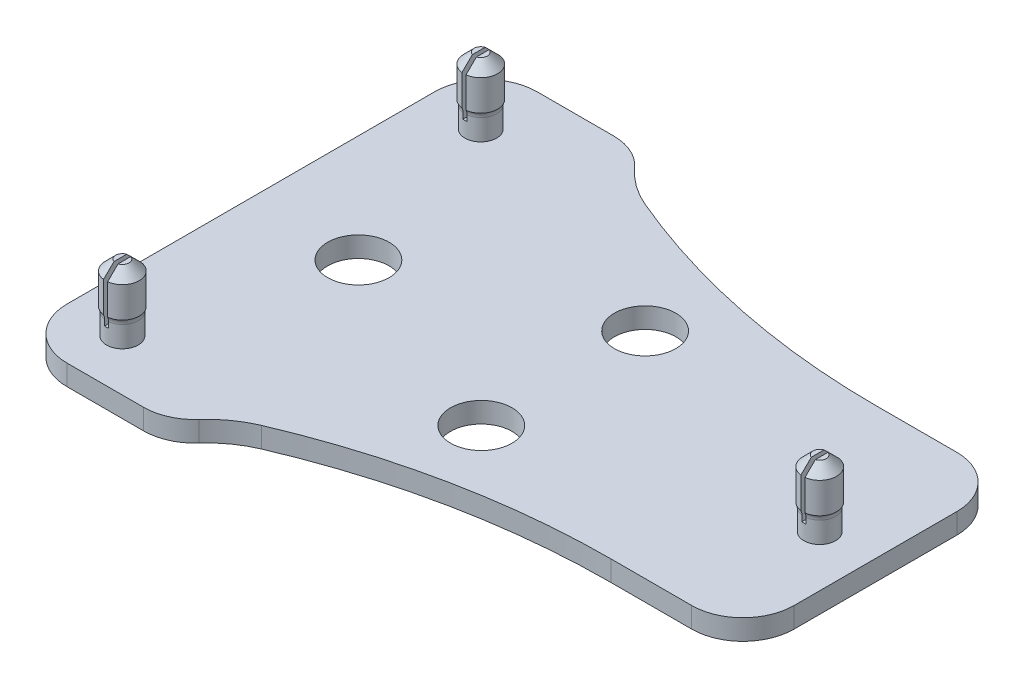
SolidWorks part; units mm, degrees
ref_plane "Front Plane" through (0, 0, 0) normal (0, 0, 1) x (1, 0, 0)
ref_plane "Top Plane" through (0, 0, 0) normal (0, 1, 0) x (1, 0, 0)
ref_plane "Right Plane" through (0, 0, 0) normal (1, 0, 0) x (0, 0, -1)
sketch "Sketch1" plane through (0, 0, 0) normal (0, 1, 0) x (1, 0, 0)
  line L0 (-30.5, -22.95) -> (-30.5, 22.95)
  line L1 (28.5, -20.95) -> (-28.5, -20.95) construction
  line L2 (28.5, -20.95) -> (28.5, 20.95) construction
  line L3 (28.5, 20.95) -> (-28.5, 20.95) construction
  line L4 (-28.5, -20.95) -> (-28.5, 20.95) construction
  line L5 (28.5, -20.95) -> (-28.5, 20.95) construction
  line L6 (28.5, 20.95) -> (-28.5, -20.95) construction
  line L7 (-15.5, 22.95) -> (-30.5, 22.95)
  line L8 (30.5, -12.95) -> (30.5, 12.95)
  line L9 (-15.5, -22.95) -> (-30.5, -22.95)
  line L10 (0, 0) -> (-42.2176, 0) construction
  line L11 (-15.5, 22.95) -> (-15.5, 11.3939) construction
  line L12 (30.5, 12.95) -> (17.6169, 12.95) construction
  line L13 (17.6169, 12.95) -> (-11.7527, 12.95) construction
  line L14 (-15.5, 22.95) -> (-15.5, 20.95)
  line L15 (17.6169, 12.95) -> (30.5, 12.95)
  line L16 (17.6169, -12.95) -> (30.5, -12.95)
  line L17 (-15.5, -22.95) -> (-15.5, -20.95)
  line L18 (30.5, 22.95) -> (-30.5, 22.95) construction
  line L19 (30.5, -22.95) -> (30.5, 22.95) construction
  line L20 (30.5, -22.95) -> (-30.5, -22.95) construction
  arc A3 (-15.5, 20.95) -> (17.6169, 12.95) centre (17.6169, 85.4958) ccw
  arc A4 (-15.5, -20.95) -> (17.6169, -12.95) centre (17.6169, -85.4958) cw
  point P0 (0, 0)
  dimension "D1" = 41.9
  dimension "D2" = 57
  dimension "D9" = 15
  dimension "D10" = 10
  dimension "D3" = 2
extrude "Boss-Extrude1" add sketch "Sketch1" along normal blind 2
fillet "Fillet1" radius 10 2 edges at (-15.5, 1, 20.95) (-15.5, 1, -20.95)
fillet "Fillet2" radius 5 6 edges at (-30.5, 1, -22.95) (-30.5, 1, 22.95) (-15.5, 1, 22.95) (-15.5, 1, -22.95) (30.5, 1, -12.95) (30.5, 1, 12.95)
ref_plane "Plane1" through (-15.5, 0, 0) normal (-1, 0, 0) x (0, 0, 1)
sketch "Sketch10" plane through (0, 2, 0) normal (0, 1, 0) x (1, 0, 0)
  line L0 (-20, 0) -> (0, 0) construction
  line L1 (0, 0) -> (0, 8) construction
  circle A0 centre (-20, 0) radius 3
  circle A1 centre (0, 8) radius 3
  circle A2 centre (0, -8) radius 3
sketch "Sketch11" plane through (0, 2, 0) normal (0, 1, 0) x (1, 0, 0)
  line L0 (-25.1, 18.65) -> (-25.1, 15.45) construction
  circle A0 centre (-25.1, 17.05) radius 1.6 construction
  circle A1 centre (-25.1, 17.05) radius 1.55
  circle A2 centre (-25.1, -17.95) radius 1.55
  circle A4 centre (25.5, -0.45) radius 1.55
  circle A5 centre (25.5, -0.45) radius 1.55
extrude "Cut-Extrude2" cut sketch "Sketch10" against normal through all
extrude "Boss-Extrude3" add sketch "Sketch11" along normal blind 6.5 contours L0 A1 | A1 L0 | A4 | A2 region at (-24.4422, 2, -17.05) region at (-25.7578, 2, -17.05) region at (-25.1, 2, 17.95) region at (25.5, 2, 0.45)
sketch "Sketch13" plane through (0, 8.5, 0) normal (0, 1, 0) x (1, 0, 0)
  circle A0 centre (-25.1, 17.05) radius 1.65
  circle A1 centre (-25.1, -17.95) radius 1.65
  circle A2 centre (25.5, -0.45) radius 1.65
extrude "Boss-Extrude4" add sketch "Sketch13" against normal blind 4
chamfer "Chamfer1" distance 1 angle 45 3 edges at (25.5, 8.5, 2.1) (-25.1, 8.5, 19.6) (-25.1, 8.5, -15.4)
sketch "Sketch14" plane through (0, 8.5, 0) normal (0, 1, 0) x (1, 0, 0)
  line L1 (-24.9, 21.0151) -> (-25.3, 21.0151)
  line L2 (-24.9, 21.0151) -> (-24.9, 13.0849)
  line L3 (-24.9, 13.0849) -> (-25.3, 13.0849)
  line L4 (-25.3, 21.0151) -> (-25.3, 13.0849)
  line L5 (-24.9, 21.0151) -> (-25.3, 13.0849) construction
  line L6 (-24.9, 13.0849) -> (-25.3, 21.0151) construction
  line L7 (-24.9, -14.6267) -> (-25.3, -14.6267)
  line L8 (-24.9, -14.6267) -> (-24.9, -21.2733)
  line L9 (-24.9, -21.2733) -> (-25.3, -21.2733)
  line L10 (-25.3, -14.6267) -> (-25.3, -21.2733)
  line L11 (-24.9, -14.6267) -> (-25.3, -21.2733) construction
  line L12 (-24.9, -21.2733) -> (-25.3, -14.6267) construction
  line L13 (25.7, 3.7668) -> (25.3, 3.7668)
  line L14 (25.7, 3.7668) -> (25.7, -4.6668)
  line L15 (25.7, -4.6668) -> (25.3, -4.6668)
  line L16 (25.3, 3.7668) -> (25.3, -4.6668)
  line L17 (25.7, 3.7668) -> (25.3, -4.6668) construction
  line L18 (25.7, -4.6668) -> (25.3, 3.7668) construction
  point P0 (-25.1, 17.05)
  point P6 (-25.1, -17.95)
  point P12 (25.5, -0.45)
extrude "Cut-Extrude3" cut sketch "Sketch14" against normal blind 5
fillet "Fillet3" radius 1 6 edges at (-23.55, 4.5, -17.05) (-26.65, 4.5, -17.05) (-23.55, 4.5, 17.95) (-26.65, 4.5, 17.95) (23.95, 4.5, 0.45) (27.05, 4.5, 0.45)
